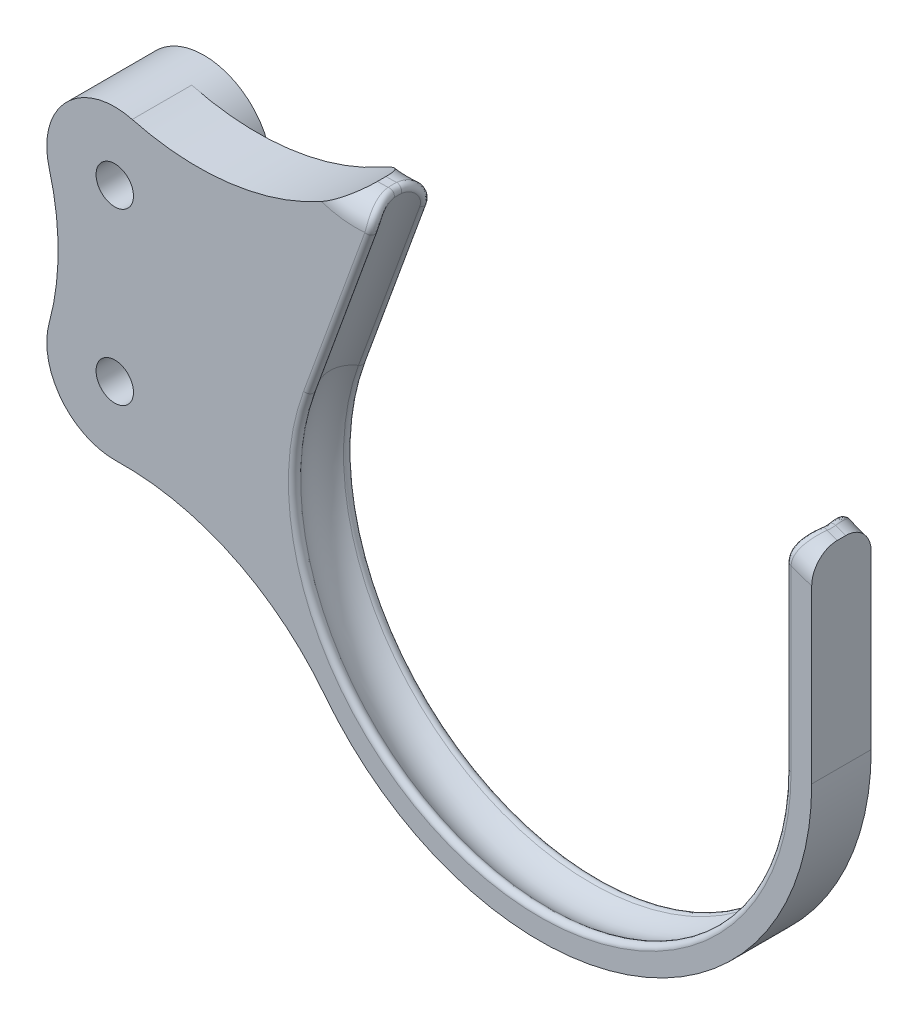
SolidWorks part; units mm, degrees
material "ABS"
ref_plane "Plan de face" through (0, 0, 0) normal (0, 0, 1) x (1, 0, 0)
ref_plane "Plan de dessus" through (0, 0, 0) normal (0, 1, 0) x (1, 0, 0)
ref_plane "Plan de droite" through (0, 0, 0) normal (1, 0, 0) x (0, 0, -1)
sketch "Esquisse1" plane through (0, 0, 0) normal (0, 0, 1) x (1, 0, 0)
  line L0 (-7.3356, 17.8353) -> (-12.2139, 4.4521)
  line L1 (13, 14.2446) -> (13, 0)
  line L2 (-11.0413, 16.4291) -> (-8.2227, 15.4017) construction
  line L3 (16, 11.6544) -> (16, 0)
  line L4 (13, 11.6544) -> (16, 11.6544) construction
  arc A0 (-23.9741, 13.8662) -> (-11.0413, 16.4291) centre (-20.1268, 28.3644) ccw
  arc A1 (16, 0) -> (-12.6452, -9.8031) centre (0, 0) cw
  circle A2 centre (-25, 10) radius 1.1
  circle A3 centre (-25, 0) radius 1.1
  arc A4 (-23.9741, 13.8662) -> (-28.859, 8.9474) centre (-25, 10) ccw
  arc A5 (-28.859, 1.0526) -> (-24.8947, -3.9986) centre (-25, 0) ccw
  arc A6 (-28.859, 1.0526) -> (-28.859, 8.9474) centre (-43.3303, 5) ccw
  arc A7 (-12.6452, -9.8031) -> (-24.8947, -3.9986) centre (-24.5, -18.9934) ccw
  arc A8 (-11.0413, 16.4291) -> (-7.3356, 17.8353) centre (-10.8171, 21.4241) ccw
  arc A9 (13, 14.2446) -> (16, 11.6544) centre (17.5, 16.4241) ccw
  circle A10 centre (-10.8171, 21.4241) radius 2 construction
  circle A11 centre (17.5, 16.4241) radius 2 construction
  arc A12 (-12.2139, 4.4521) -> (13, 0) centre (0, 0) ccw
  dimension "D1" = 10
  dimension "D2" = 25
  dimension "D3" = 2.2
  dimension "D4" = 4
  dimension "D5" = 5
  dimension "D6" = 15
  dimension "D8" = 13
  dimension "D11" = 16
  dimension "D9" = 4.5
  dimension "D10" = 4.5
extrude "Boss.-Extru.1" add sketch "Esquisse1" along normal mid plane 3.5
sketch "Esquisse2" plane through (0, 0, 0) normal (0, 0, 1) x (1, 0, 0)
  circle A0 centre (-25, 10) radius 4
  circle A1 centre (-25, 10) radius 1.1
  circle A2 centre (-25, 0) radius 1.1
  circle A3 centre (-25, 0) radius 4
  circle A4 centre (-25, 10) radius 1.1 construction
  circle A5 centre (-25, 0) radius 1.1 construction
  arc A6 (-28.859, 1.0526) -> (-24.8947, -3.9986) centre (-25, 0) ccw construction
  arc A7 (-23.9741, 13.8662) -> (-28.859, 8.9474) centre (-25, 10) ccw construction
extrude "Boss.-Extru.2" add sketch "Esquisse2" against normal blind 3.5
sketch "Esquisse3" plane through (0, 0, 0) normal (0, 0, 1) x (1, 0, 0)
  line L0 (-12.2139, 4.4521) -> (-7.3356, 17.8353) construction
  line L1 (13, 14.2446) -> (13, 0) construction
  line L2 (-12.2139, 4.4521) -> (-7.3356, 17.8353)
  line L3 (13, 14.2446) -> (13, 0)
  arc A0 (-12.2139, 4.4521) -> (13, 0) centre (0, 0) ccw construction
  arc A1 (-12.2139, 4.4521) -> (13, 0) centre (0, 0) ccw
ref_plane "Plan1" through (-7.3356, 17.8353, 0) normal (0.3425, 0.9395, 0) x (0.9395, -0.3425, 0)
sketch "Esquisse4" plane through (-7.3356, 17.8353, 0) normal (0.3425, 0.9395, 0) x (0.9395, -0.3425, 0)
  circle A0 centre (0, 0) radius 2
  dimension "D1" = 4
sweep "Enlèvement de matière-Balayage1" cut profiles "Esquisse4" path "Esquisse3"
fillet "Congé1" radius 1.5 4 edges at (14.91, 12.1472, 1.75) (14.91, 12.1472, -1.75) (-9.8484, 16.5188, -1.75) (-9.8484, 16.5188, 1.75)
fillet "Congé2" radius 0.3 12 edges at (14.3842, 11.7811, 1.4436) (14.2845, 11.69, -1.533) (-9.4173, 15.875, 1.533) (-9.4797, 15.9948, -1.4436) (-11.2456, 9.9357, -1.75) (-2.4288, -13.7555, -1.75) (13.9682, 5.4836, -1.75) (13.9682, 5.4836, 1.75) (-2.4288, -13.7555, 1.75) (-11.2456, 9.9357, 1.75)
